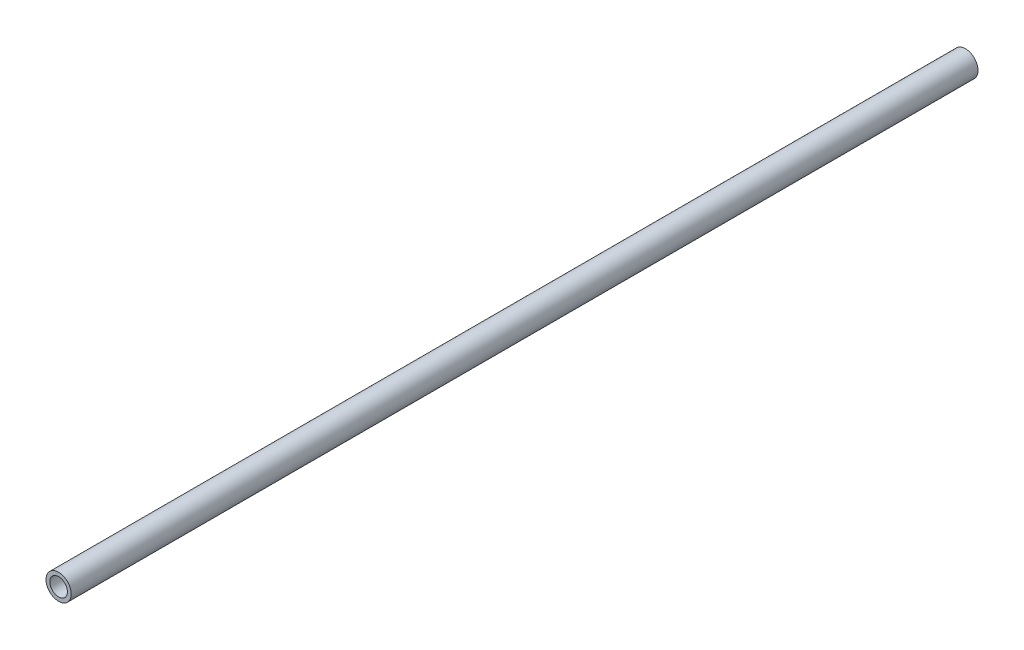
SolidWorks part; units mm, degrees
ref_plane "Front Plane" through (0, 0, 0) normal (0, 0, 1) x (1, 0, 0)
ref_plane "Top Plane" through (0, 0, 0) normal (0, 1, 0) x (1, 0, 0)
ref_plane "Right Plane" through (0, 0, 0) normal (1, 0, 0) x (0, 0, -1)
sketch "Sketch1" plane through (0, 0, 0) normal (0, 0, 1) x (1, 0, 0)
  circle A0 centre (0, 0) radius 10
  circle A1 centre (0, 0) radius 7
  dimension "D1" = 20
extrude "Boss-Extrude1" add sketch "Sketch1" along normal blind 720
